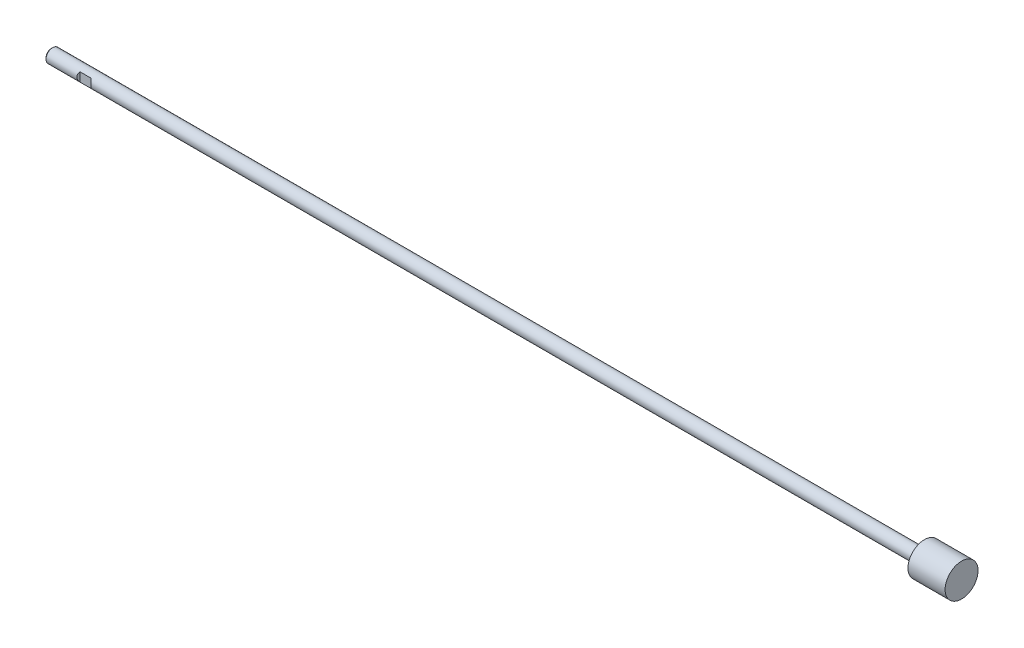
SolidWorks part; units mm, degrees
ref_plane "前视基准面" through (0, 0, 0) normal (0, 0, 1) x (1, 0, 0)
ref_plane "上视基准面" through (0, 0, 0) normal (0, 1, 0) x (1, 0, 0)
ref_plane "右视基准面" through (0, 0, 0) normal (1, 0, 0) x (0, 0, -1)
sketch "草图1" plane through (0, 0, 0) normal (0, 0, 1) x (1, 0, 0)
  line L0 (0, 0) -> (0, 3.233)
  line L1 (0, 3.233) -> (0.767, 4)
  line L2 (0.767, 4) -> (517, 4)
  line L3 (517, 4) -> (517, 9.75)
  line L4 (517, 9.75) -> (539, 9.75)
  line L5 (539, 9.75) -> (539, 0)
  line L6 (539, 0) -> (0, 0)
  line L7 (539, 0) -> (0, 0) construction
revolve "旋转1" add sketch "草图1" angle 360 about L7 reverse direction yes
cosmetic thread "装饰螺纹线1" parameters "D1"=18.75, "D2"=6.466
ref_plane "基准面4" through (28, 0, 0) normal (1, 0, 0) x (0, 0, -1)
ref_plane "基准面5" through (10, 0, 0) normal (1, 0, 0) x (0, 0, -1)
sketch "草图2" plane through (0, 0, 0) normal (0, 1, 0) x (1, 0, 0)
  line L0 (-5, -12) -> (35.4, -12)
  line L1 (35.4, -12) -> (26.4, -3)
  line L2 (26.4, -3) -> (20, -3)
  line L3 (20, -3) -> (18, -5)
  line L4 (18, -5) -> (18, -10)
  line L5 (18, -10) -> (-3, -10)
  line L6 (-3, -10) -> (-3, 10)
  line L7 (-3, 10) -> (18, 10)
  line L8 (18, 10) -> (18, 5)
  line L9 (18, 5) -> (20, 3)
  line L10 (20, 3) -> (26.4, 3)
  line L11 (26.4, 3) -> (35.4, 12)
  line L12 (35.4, 12) -> (-5, 12)
  line L13 (-5, 12) -> (-5, -12)
extrude "切除-拉伸1" cut sketch "草图2" along normal blind 3 and the other way blind 3
ref_plane "基准面6" through (0, 0, 0) normal (0, -0.7071, 0.7071) x (1, 0, 0)
ref_plane "基准面7" through (0, 0, 0) normal (0, -0.7071, -0.7071) x (-1, 0, 0)
ref_plane "nut-rod XY" through (10, 0, 0) normal (-1, 0, 0) x (0, 0, 1)
ref_plane "nut-rod XZ" through (0, 0, 0) normal (0, 1, 0) x (1, 0, 0)
ref_plane "nut-rod YZ" through (0, 0, 0) normal (0, 0, -1) x (-1, 0, 0)
ref_axis "nut-rod X" through (10, 0, 80.9) along (0, 0, -1)
ref_axis "nut-rod Y" through (10, 50, 0) along (0, -1, 0)
ref_axis "nut-rod Z" through (-80.9, 0, 0) along (1, 0, 0)
sketch3d "nut-rod"
  point P0 (10, 0, 0)
ref_plane "rod XY" through (28, 0, 0) normal (-1, 0, 0) x (0, 0, 1)
ref_plane "rod XZ" through (0, 0, 0) normal (0, 1, 0) x (1, 0, 0)
ref_plane "rod YZ" through (0, 0, 0) normal (0, 0, -1) x (-1, 0, 0)
ref_axis "rod X" through (28, 0, 80.9) along (0, 0, -1)
ref_axis "rod Y" through (28, 50, 0) along (0, -1, 0)
ref_axis "rod Z" through (-80.9, 0, 0) along (1, 0, 0)
sketch3d "rod"
  point P0 (28, 0, 0)
